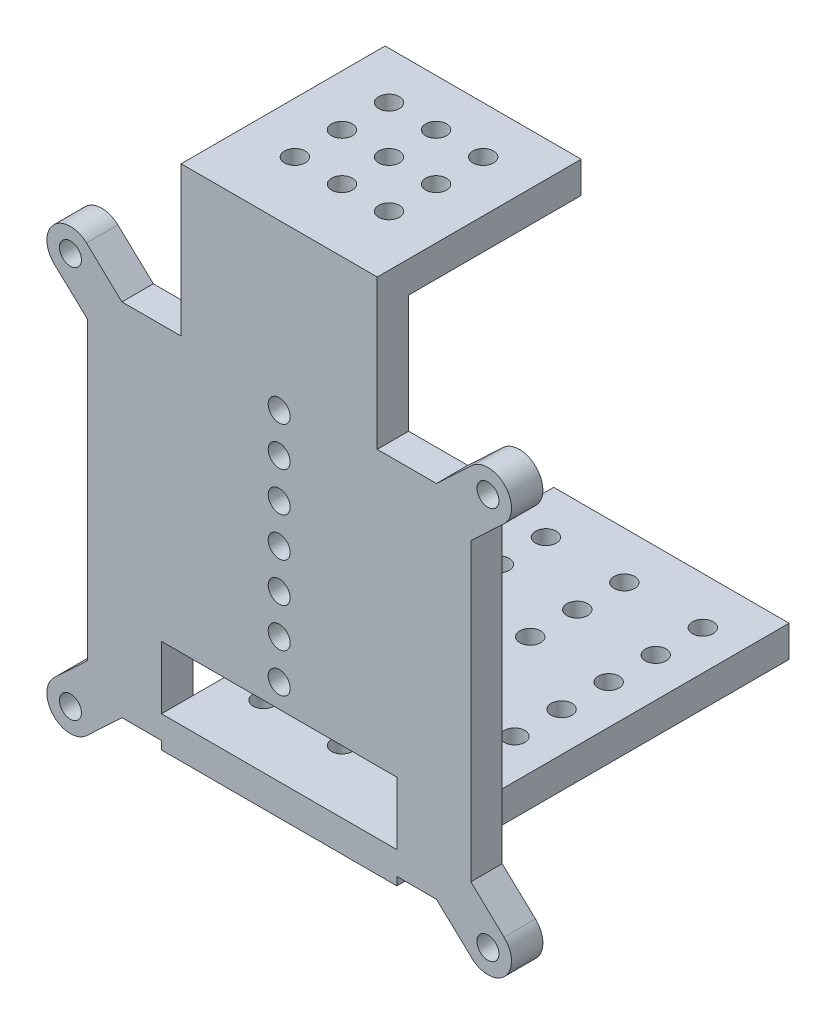
SolidWorks part; units mm, degrees
ref_plane "前视基准面" through (0, 0, 0) normal (0, 0, 1) x (1, 0, 0)
ref_plane "上视基准面" through (0, 0, 0) normal (0, 1, 0) x (1, 0, 0)
ref_plane "右视基准面" through (0, 0, 0) normal (1, 0, 0) x (0, 0, -1)
sketch "草图1" plane through (0, 0, 0) normal (0, 0, 1) x (1, 0, 0)
  line L0 (0, 39) -> (0, -19) construction
  line L1 (-12.5, 39) -> (12.5, 39)
  line L2 (-12.5, 39) -> (-12.5, -19)
  line L3 (-12.5, -19) -> (12.5, -19)
  line L4 (12.5, 39) -> (12.5, -19)
  line L5 (-12.5, 10) -> (12.5, 10) construction
  line L6 (-12.5, 29) -> (12.5, 29) construction
  circle A0 centre (0, 22) radius 1.4
  circle A7 centre (0, 17) radius 1.4
  circle A8 centre (0, 12) radius 1.4
  circle A9 centre (0, 7) radius 1.4
  circle A10 centre (0, 2) radius 1.4
  circle A11 centre (0, -3) radius 1.4
  circle A12 centre (0, -8) radius 1.4
  circle A13 centre (0, -13) radius 1.4
  dimension "D1" = 25
  dimension "D3" = 2.8
  dimension "D9" = 5
  dimension "D2" = 10
  dimension "D4" = 7
  dimension "D5" = 58
  dimension "D6" = 10
  dimension "D7" = 1
  dimension "D8" = 8
extrude "凸台-拉伸1" add sketch "草图1" along normal blind 4
sketch "草图2" plane through (0, 0, 0) normal (0, 0, 1) x (1, 0, 0)
  line L0 (0, 39) -> (0, -19) construction
  line L2 (-12.5, 29) -> (12.5, 29) construction
  circle A0 centre (26.6113, 26) radius 1.4
  circle A1 centre (-26.6113, 26) radius 1.4
  circle A2 centre (-26.6113, -24.0086) radius 1.4
  circle A3 centre (26.6113, -24.0086) radius 1.4
  line B0 (0, 21.9457) -> (0, -19.9543) construction
  line B1 (-22.425, 21.9457) -> (22.425, 21.9457)
  line B2 (-22.425, 21.9457) -> (-22.425, -19.9543)
  line B3 (-22.425, -19.9543) -> (22.425, -19.9543)
  line B4 (22.425, 21.9457) -> (22.425, -19.9543)
  line B5 (-22.425, 0.9957) -> (22.425, 0.9957) construction
  line B6 (-24.425, 23.9457) -> (24.425, 23.9457)
  line B7 (-15.275, -14.2793) -> (15.275, -14.2793)
  line B8 (-15.275, -14.2793) -> (-15.275, 16.2707)
  line B9 (-15.275, 16.2707) -> (15.275, 16.2707)
  line B10 (15.275, -14.2793) -> (15.275, 16.2707)
  line B11 (-15.275, -14.2793) -> (15.275, 16.2707) construction
  line B12 (-15.275, 16.2707) -> (15.275, -14.2793) construction
  line B13 (24.425, 23.9457) -> (24.425, -21.9543)
  line B14 (-24.425, -21.9543) -> (24.425, -21.9543)
  line B15 (-24.425, 23.9457) -> (-24.425, -21.9543)
  line B16 (-24.425, 23.9457) -> (24.425, -21.9543) construction
  line B17 (7.0496, -1.2543) -> (11.5496, -1.2543)
  line B18 (7.0496, -1.2543) -> (7.0496, 3.2457) construction
  line B19 (7.0496, 3.2457) -> (11.5496, 3.2457)
  line B20 (11.5496, -1.2543) -> (11.5496, 3.2457)
  line B21 (7.0496, -1.2543) -> (11.5496, 3.2457) construction
  line B22 (7.0496, 3.2457) -> (11.5496, -1.2543) construction
  line B23 (24.425, 23.9457) -> (-24.425, -21.9543) construction
  line B24 (-28.6656, 23.8137) -> (-24.425, 19.8292)
  line B25 (-24.557, 28.1863) -> (-20.0439, 23.9457)
  line B26 (-24.557, -26.1949) -> (-20.0439, -21.9543)
  line B27 (-28.6656, -21.8222) -> (-24.425, -17.8377)
  line B28 (28.6656, -21.8222) -> (24.425, -17.8377)
  line B29 (24.557, -26.1949) -> (20.0439, -21.9543)
  line B30 (24.557, 28.1863) -> (20.0439, 23.9457)
  line B31 (28.6656, 23.8137) -> (24.425, 19.8292)
  circle B32 centre (0, 0.9957) radius 7.4
  circle B33 centre (0, 0.9957) radius 11.25
  circle B34 centre (0, 0.9957) radius 9.05
  circle B35 centre (-26.6113, 26) radius 1.25
  circle B36 centre (-26.6113, 26) radius 3
  circle B37 centre (-26.6113, -24.0086) radius 3
  circle B38 centre (-26.6113, -24.0086) radius 1.25
  circle B39 centre (26.6113, -24.0086) radius 1.25
  circle B40 centre (26.6113, -24.0086) radius 3
  circle B41 centre (26.6113, 26) radius 3
  circle B42 centre (26.6113, 26) radius 1.25
  dimension "D1" = 2.8
sketch_block_instance "camera_holder-1"
sketch_block "camera_holder" parameters "D4"=14.8, "D5"=22.5, "D6"=18.1, "D9"=2.5, "D1"=44.85, "D2"=41.9, "D3"=30.55, "D7"=4.5, "D8"=4.5, "D10"=3
extrude "凸台-拉伸2" add sketch "草图2" along normal up to surface (4 mm away) contours B41 B42 | B6 B41 B30 | B31 B41 B13 | B40 B28 B13 | B40 B14 B29 | B40 B39 | B14 B37 B26 | B27 B37 B15 | B37 B38 | B36 B24 B15 | B36 B6 B25 | B36 B35 | B6 B15 B14 B13 B1 B4 B3 B2 | B7 B10 B9 B8 B33 B19 B20 B17 | B4 B1 B2 B3 B10 B7 B8 B9 region at (0, 21.332, 0) region at (-22.5782, 25.0849, 0) region at (-22.2344, 23.2754, 0) region at (-25.5484, 22.115, 0) region at (-26.5206, 23.0863, 0) region at (22.5782, 25.0849, 0) region at (-25.5484, -20.1236, 0) region at (25.5484, 22.115, 0) region at (23.6976, 26.0907, 0) region at (-22.5782, -23.0934, 0) region at (-23.901, -22.935, 0) region at (25.5484, -20.1236, 0) region at (22.5782, -23.0934, 0) region at (26.5206, -21.0948, 0) region at (-14.843, 0.9957, 0) up to face at (1.4, 2, 4)
extrude "切除-拉伸1" cut sketch "草图1<2>" against normal up to next from surface contours A0 | A7 | A8 | A13 starting at face at (0, 11.4229, 4)
sketch "草图1<2>" plane through (0, 0, 0) normal (0, 0, 1) x (1, 0, 0) same geometry as "草图1"
sketch "草图3" plane through (0, 0, 0) normal (0, 0, 1) x (1, 0, 0)
  line L0 (-12.5, -19) -> (12.5, -19) construction
  line L1 (-15, -19) -> (15, -19)
  line L2 (-15, -19) -> (-15, -23)
  line L3 (-15, -23) -> (15, -23)
  line L4 (15, -19) -> (15, -23)
  line L5 (0, -23) -> (0, -19) construction
  line L6 (0, 39) -> (0, -19) construction
  line L7 (0, 42.9695) -> (0, 38.9695) construction
  line L8 (-12.5, 42.9695) -> (12.5, 42.9695)
  line L9 (-12.5, 42.9695) -> (-12.5, 38.9695)
  line L10 (-12.5, 38.9695) -> (12.5, 38.9695)
  line L11 (12.5, 42.9695) -> (12.5, 38.9695)
  line L12 (12.5, 39) -> (12.5, -19) construction
  dimension "D1" = 30
  dimension "D2" = 4
  dimension "D3" = 4
extrude "凸台-拉伸3" add sketch "草图3" against normal blind 26 from surface contours L11 L8 L9 L10 region at (0, 40.9695, 0) starting at face at (1.4, 22, 4)
sketch "草图4" plane through (0, 42.9695, 0) normal (0, 1, 0) x (1, 0, 0)
  line L0 (0, 22) -> (0, -4) construction
  line L3 (-1.4, 0) -> (1.4, 0) construction
  circle A0 centre (0, 4) radius 1.325
  circle A1 centre (6, 4) radius 1.325
  circle A2 centre (6, 10) radius 1.325
  circle A3 centre (0, 10) radius 1.325
  circle A4 centre (0, 16) radius 1.325
  circle A5 centre (6, 16) radius 1.325
  circle A6 centre (-6, 4) radius 1.325
  circle A7 centre (-6, 10) radius 1.325
  circle A8 centre (-6, 16) radius 1.325
  dimension "D1" = 2.65
  dimension "D5" = 6
  dimension "D6" = 6
  dimension "D2" = 4
  dimension "D3" = 2
  dimension "D4" = 3
extrude "切除-拉伸2" cut sketch "草图4" against normal up to next from surface contours A8 | A4 | A5 | A7 | A3 | A2 | A1 | A0 | A6 starting at face at (0, 42.9695, -9)
extrude "凸台-拉伸4" add sketch "草图3<3>" against normal blind 50 from surface contours L4 L1 L2 L3 region at (0, -21, 0) starting at face at (0, 7.4881, 4)
sketch "草图3<3>" plane through (0, 0, 0) normal (0, 0, 1) x (1, 0, 0) same geometry as "草图3"
sketch "草图5" plane through (0, -23, 0) normal (0, -1, 0) x (1, 0, 0)
  line L0 (0, -46) -> (0, 4) construction
  line L1 (15, -46) -> (-15, -46) construction
  line L2 (15, 4) -> (-15, 4) construction
  line L3 (-12.5, 0) -> (12.5, 0) construction
  circle A0 centre (0, -4) radius 1.325
  circle A1 centre (10, -4) radius 1.325
  circle A2 centre (10, -10) radius 1.325
  circle A3 centre (10, -16) radius 1.325
  circle A4 centre (10, -22) radius 1.325
  circle A5 centre (10, -28) radius 1.325
  circle A6 centre (10, -34) radius 1.325
  circle A7 centre (10, -40) radius 1.325
  circle A8 centre (0, -10) radius 1.325
  circle A9 centre (0, -16) radius 1.325
  circle A10 centre (0, -22) radius 1.325
  circle A11 centre (0, -28) radius 1.325
  circle A12 centre (0, -34) radius 1.325
  circle A13 centre (0, -40) radius 1.325
  circle A14 centre (-10, -40) radius 1.325
  circle A15 centre (-10, -34) radius 1.325
  circle A16 centre (-10, -28) radius 1.325
  circle A17 centre (-10, -22) radius 1.325
  circle A18 centre (-10, -16) radius 1.325
  circle A19 centre (-10, -10) radius 1.325
  circle A20 centre (-10, -4) radius 1.325
  dimension "D1" = 2.65
  dimension "D5" = 6
  dimension "D2" = 4
  dimension "D3" = 2
  dimension "D4" = 7
extrude "切除-拉伸3" cut sketch "草图5" against normal up to next and the other way through all
sketch "草图6" plane through (0, 0, 4) normal (0, 0, 1) x (1, 0, 0)
  line L0 (0, -11) -> (0, -19) construction
  line L1 (-15, -11) -> (15, -11)
  line L2 (-15, -11) -> (-15, -19)
  line L3 (-15, -19) -> (15, -19)
  line L4 (15, -11) -> (15, -19)
  line L5 (0, 39) -> (0, -19) construction
  line L6 (1.325, -19) -> (-1.325, -19) construction
  dimension "D1" = 30
  dimension "D2" = 8
extrude "切除-拉伸4" cut sketch "草图6" against normal blind 50
